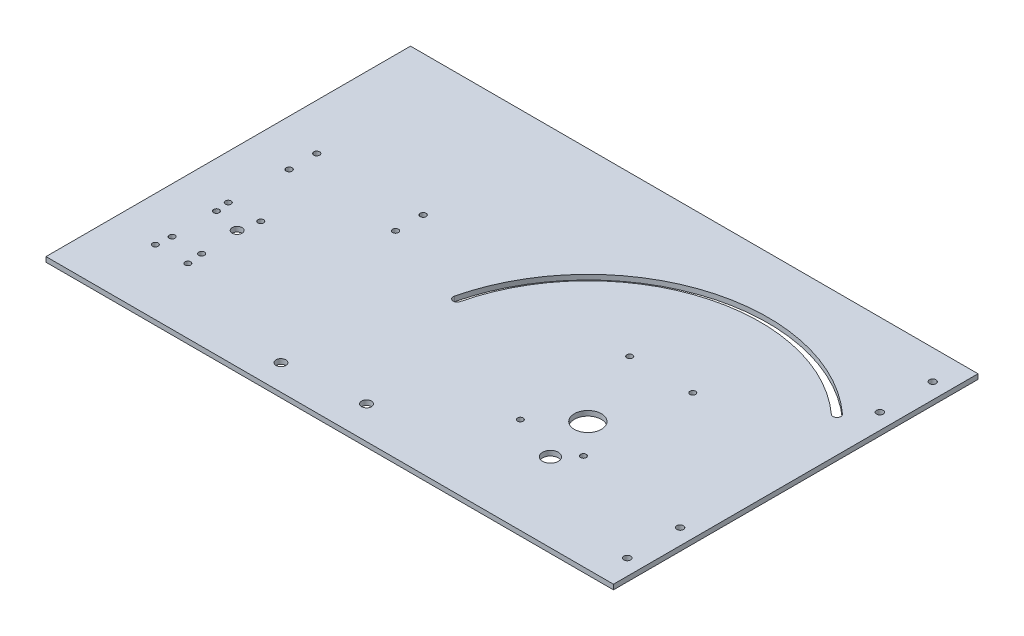
SolidWorks part; units mm, degrees
ref_plane "Front Plane" through (0, 0, 0) normal (0, 0, 1) x (1, 0, 0)
ref_plane "Top Plane" through (0, 0, 0) normal (0, 1, 0) x (1, 0, 0)
ref_plane "Right Plane" through (0, 0, 0) normal (1, 0, 0) x (0, 0, -1)
sketch "Sketch1" plane through (0, 0, 0) normal (0, 1, 0) x (1, 0, 0)
  line L1 (-158.75, 88.9) -> (158.75, 88.9)
  line L2 (-158.75, 88.9) -> (-158.75, -88.9)
  line L3 (-158.75, -88.9) -> (158.75, -88.9)
  line L4 (158.75, 88.9) -> (158.75, -88.9)
  line L5 (-158.75, 88.9) -> (158.75, -88.9) construction
  line L6 (-158.75, -88.9) -> (158.75, 88.9) construction
  circle A0 centre (-111.76, -12.7) radius 3.175
  circle A1 centre (107.95, -6.35) radius 8.7313
  circle A4 centre (-129.032, 55.88) radius 1.905
  circle A5 centre (-60.452, 55.88) radius 1.905
  circle A7 centre (-129.032, 38.1) radius 1.905
  circle A8 centre (-60.452, 38.1) radius 1.905
  point P0 (0, 0)
  dimension "D3" = 6.35
  dimension "D4" = 17.4625
  dimension "D14" = 3.81
  dimension "D17" = 17.78
  dimension "D1" = 317.5
  dimension "D2" = 177.8
  dimension "D5" = 46.99
  dimension "D6" = 266.7
  dimension "D7" = 95.25
  dimension "D8" = 76.2
  dimension "D13" = 29.718
  dimension "D15" = 68.58
  dimension "D16" = 127
extrude "Boss-Extrude1" add sketch "Sketch1" along normal blind 3.175
sketch "Sketch2" plane through (0, 3.175, 0) normal (0, 1, 0) x (1, 0, 0)
  line L0 (-158.75, 88.9) -> (-158.75, -88.9) construction
  line L1 (-158.75, -88.9) -> (158.75, -88.9) construction
  circle A0 centre (-89.0817, -33.177) radius 1.905
  circle A1 centre (-132.1376, -36.4483) radius 1.905
  dimension "D1" = 3.81
  dimension "D2" = 69.6683
  dimension "D3" = 52.4517
  dimension "D4" = 55.723
  dimension "D5" = 43.18
extrude "Cut-Extrude1" [suppressed] cut sketch "Sketch2" against normal through all
sketch "Sketch3" plane through (0, 0, 0) normal (0, -1, 0) x (-1, 0, 0)
  line L0 (158.75, -88.9) -> (-158.75, -88.9) construction
  line L1 (158.75, 88.9) -> (158.75, -88.9) construction
  circle A0 centre (23.8295, -72.39) radius 3.175
  circle A1 centre (-26.7643, -67.818) radius 3.175
  dimension "D1" = 6.35
  dimension "D2" = 4.572
  dimension "D3" = 16.51
  dimension "D4" = 185.5143
  dimension "D5" = 50.8
extrude "Cut-Extrude2" cut sketch "Sketch3" against normal through all
sketch "Sketch4" plane through (0, 3.175, 0) normal (0, 1, 0) x (1, 0, 0)
  line L0 (-158.75, -88.9) -> (158.75, -88.9) construction
  line L1 (158.75, 88.9) -> (133.35, 88.9)
  line L2 (158.75, 88.9) -> (158.75, -88.9)
  line L3 (158.75, -88.9) -> (133.35, -88.9)
  line L4 (133.35, 88.9) -> (133.35, -88.9)
  dimension "D1" = 25.4
extrude "Cut-Extrude3" cut sketch "Sketch4" against normal through all
sketch "Sketch5" plane through (0, 3.175, 0) normal (0, 1, 0) x (1, 0, 0)
  line L0 (133.35, 88.9) -> (-158.75, 88.9) construction
  line L1 (133.35, 88.9) -> (133.35, -88.9) construction
  circle A0 centre (115.57, -38.1) radius 5.08
  dimension "D3" = 10.16
  dimension "D1" = 127
  dimension "D2" = 17.78
extrude "Cut-Extrude4" cut sketch "Sketch5" against normal through all
sketch "Sketch7" plane through (0, 3.175, 0) normal (0, 1, 0) x (1, 0, 0)
  line L0 (133.35, 88.9) -> (133.35, -88.9) construction
  line L1 (133.35, 88.9) -> (-158.75, 88.9) construction
  line L2 (-158.75, 88.9) -> (-158.75, -88.9) construction
  line L3 (-158.75, -88.9) -> (133.35, -88.9) construction
  circle A1 centre (125.73, 43.4975) radius 1.8415
  circle A2 centre (85.09, 43.4975) radius 1.8415
  circle A3 centre (85.09, -26.9875) radius 1.8415
  circle A4 centre (125.73, -26.9875) radius 1.8415
  circle A5 centre (-130.175, -46.99) radius 1.8415
  circle A6 centre (-109.22, -46.99) radius 1.8415
  circle A7 centre (-129.2225, -37.1475) radius 1.8415
  circle A8 centre (-110.1725, -37.1475) radius 1.8415
  circle A9 centre (-129.2225, -8.5725) radius 1.8415
  circle A10 centre (-130.175, 0) radius 1.8415
  circle A11 centre (-109.22, 0) radius 1.8415
  dimension "D1" = 7.62
  dimension "D5" = 3.683
  dimension "D10" = 3.683
  dimension "D15" = 3.683
  dimension "D2" = 40.64
  dimension "D3" = 70.485
  dimension "D4" = 61.9125
  dimension "D6" = 28.575
  dimension "D7" = 20.955
  dimension "D8" = 0.9525
  dimension "D9" = 19.05
  dimension "D11" = 88.9
  dimension "D12" = 8.5725
  dimension "D13" = 28.575
  dimension "D14" = 9.8425
extrude "Cut-Extrude6" cut sketch "Sketch7" against normal through all
sketch "Sketch8" plane through (0, 0, 0) normal (0, -1, 0) x (1, 0, 0)
  line L1 (-158.75, -88.9) -> (-158.75, 88.9) construction
  line L2 (-158.75, 88.9) -> (133.35, 88.9) construction
  line L3 (133.35, 88.9) -> (133.35, -88.9)
  line L4 (133.35, -88.9) -> (-158.75, -88.9) construction
  line L5 (133.35, -88.9) -> (-158.75, -88.9)
  line L6 (-158.75, -88.9) -> (-158.75, -146.05)
  line L7 (-158.75, -146.05) -> (209.55, -146.05)
  line L8 (209.55, -146.05) -> (209.55, 88.9)
  line L9 (209.55, 88.9) -> (133.35, 88.9)
  line L12 (133.35, -88.9) -> (133.35, 88.9) construction
  dimension "D1" = 76.2
  dimension "D2" = 57.15
extrude "Boss-Extrude2" add sketch "Sketch8" against normal through all
sketch "Sketch9" plane through (0, 0, 0) normal (0, -1, 0) x (1, 0, 0)
  line L2 (209.55, -146.05) -> (209.55, 88.9) construction
  arc A0 (185.8528, -79.875) -> (182.4472, -76.1056) centre (184.15, -77.9903) ccw
  arc A1 (-0.15, -19.402) -> (-5.0917, -20.5792) centre (-2.6208, -19.9906) ccw
  circle A2 centre (107.95, 6.35) radius 113.665 construction
  arc A3 (182.4472, -76.1056) -> (-0.15, -19.402) centre (107.95, 6.35) cw
  arc A4 (185.8528, -79.875) -> (-5.0917, -20.5792) centre (107.95, 6.35) cw
  arc A5 (-5.0917, -20.5792) -> (-2.0046, -22.4547) centre (-2.6208, -19.9906) ccw construction
  arc A6 (-2.0046, -22.4547) -> (-0.15, -19.402) centre (-2.6208, -19.9906) ccw construction
  arc A7 (182.2464, -79.672) -> (185.8528, -79.875) centre (184.15, -77.9903) ccw construction
  arc A8 (182.4472, -76.1056) -> (182.2464, -79.672) centre (184.15, -77.9903) ccw construction
  circle A12 centre (107.95, 6.35) radius 8.7313 construction
  dimension "D1" = 5.08
  dimension "D6" = 227.33
  dimension "D2" = 25.4
  dimension "D5" = 186.7708
extrude "Cut-Extrude7" cut sketch "Sketch9" against normal through all
sketch "Sketch10" plane through (0, 0, 0) normal (0, -1, 0) x (1, 0, 0)
  line L0 (209.55, -146.05) -> (209.55, 88.9) construction
  line L1 (-158.75, 88.9) -> (209.55, 88.9) construction
  line L2 (209.55, -28.575) -> (142.4229, -28.575) construction
  line L3 (-158.75, -146.05) -> (209.55, -146.05) construction
  line L4 (209.55, 88.9) -> (207.01, 88.9)
  line L5 (209.55, 88.9) -> (209.55, -146.05)
  line L6 (209.55, -146.05) -> (207.01, -146.05)
  line L7 (207.01, 88.9) -> (207.01, -146.05)
  circle A0 centre (196.85, 69.85) radius 2.159
  circle A1 centre (196.85, 35.814) radius 2.159
  circle A2 centre (196.85, -92.964) radius 2.159
  circle A3 centre (196.85, -127) radius 2.159
  dimension "D2" = 4.318
  dimension "D1" = 34.036
  dimension "D3" = 12.7
  dimension "D4" = 19.05
  dimension "D5" = 2.54
extrude "Cut-Extrude8" cut sketch "Sketch10" against normal through all
